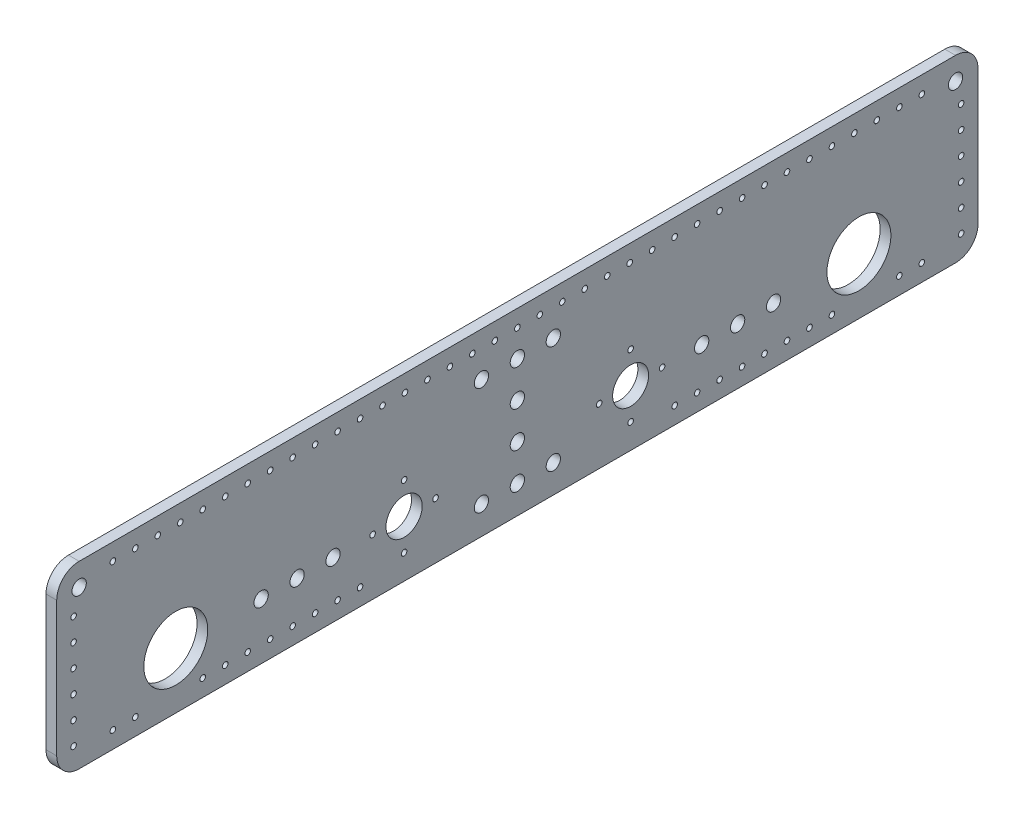
SolidWorks part; units mm, degrees
ref_plane "Front Plane" through (0, 0, 0) normal (0, 0, 1) x (1, 0, 0)
ref_plane "Top Plane" through (0, 0, 0) normal (0, 1, 0) x (1, 0, 0)
ref_plane "Right Plane" through (0, 0, 0) normal (1, 0, 0) x (0, 0, -1)
sketch "Sketch2" plane through (0, 0, 0) normal (1, 0, 0) x (0, 0, -1)
  line L0 (-23.4723, 28.6683) -> (-23.4723, -31.3317)
  line L1 (-13.4723, 38.6683) -> (376.5277, 38.6683)
  line L2 (-13.4723, -41.3317) -> (376.5277, -41.3317)
  line L3 (386.5277, 28.6683) -> (386.5277, -31.3317)
  circle A1 centre (29.5277, -16.3317) radius 14.225
  circle A2 centre (333.5277, -16.3317) radius 14.225
  arc A15 (-23.4723, 28.6683) -> (-13.4723, 38.6683) centre (-13.4723, 28.6683) cw
  arc A16 (-13.4723, -41.3317) -> (-23.4723, -31.3317) centre (-13.4723, -31.3317) cw
  arc A17 (386.5277, 28.6683) -> (376.5277, 38.6683) centre (376.5277, 28.6683) ccw
  arc A18 (376.5277, -41.3317) -> (386.5277, -31.3317) centre (376.5277, -31.3317) ccw
  circle A59 centre (181.5277, -28.7717) radius 3.18
  circle A60 centre (197.5277, -28.7717) radius 3.18
  circle A63 centre (197.5277, 19.2283) radius 3.18
  circle A64 centre (181.5277, -12.7717) radius 3.18
  circle A65 centre (181.5277, 3.2283) radius 3.18
  circle A66 centre (181.5277, 19.2283) radius 3.18
  circle A67 centre (165.5277, -28.7717) radius 3.18
  circle A68 centre (165.5277, 19.2283) radius 3.18
  circle A69 centre (197.5277, -12.7717) radius 3.18 [skipped]
  circle A70 centre (197.5277, 3.2283) radius 3.18 [skipped]
  circle A71 centre (-8.4723, 31.1683) radius 1.25 construction
  circle A150 centre (83.5027, -16.3317) radius 3.18
  circle A151 centre (279.5527, -16.3317) radius 3.18
  circle A152 centre (1.5277, 31.1683) radius 1.25
  circle A153 centre (11.5277, 31.1683) radius 1.25
  circle A154 centre (21.5277, 31.1683) radius 1.25
  circle A155 centre (31.5277, 31.1683) radius 1.25
  circle A156 centre (41.5277, 31.1683) radius 1.25
  circle A157 centre (51.5277, 31.1683) radius 1.25
  circle A158 centre (61.5277, 31.1683) radius 1.25
  circle A159 centre (71.5277, 31.1683) radius 1.25
  circle A160 centre (81.5277, 31.1683) radius 1.25
  circle A161 centre (91.5277, 31.1683) radius 1.25
  circle A162 centre (101.5277, 31.1683) radius 1.25
  circle A163 centre (111.5277, 31.1683) radius 1.25
  circle A164 centre (121.5277, 31.1683) radius 1.25
  circle A165 centre (131.5277, 31.1683) radius 1.25
  circle A166 centre (141.5277, 31.1683) radius 1.25
  circle A167 centre (151.5277, 31.1683) radius 1.25
  circle A168 centre (161.5277, 31.1683) radius 1.25
  circle A169 centre (171.5277, 31.1683) radius 1.25
  circle A170 centre (181.5277, 31.1683) radius 1.25
  circle A171 centre (191.5277, 31.1683) radius 1.25
  circle A172 centre (201.5277, 31.1683) radius 1.25
  circle A173 centre (211.5277, 31.1683) radius 1.25
  circle A174 centre (221.5277, 31.1683) radius 1.25
  circle A175 centre (231.5277, 31.1683) radius 1.25
  circle A176 centre (241.5277, 31.1683) radius 1.25
  circle A177 centre (251.5277, 31.1683) radius 1.25
  circle A178 centre (261.5277, 31.1683) radius 1.25
  circle A179 centre (271.5277, 31.1683) radius 1.25
  circle A180 centre (281.5277, 31.1683) radius 1.25
  circle A181 centre (291.5277, 31.1683) radius 1.25
  circle A182 centre (301.5277, 31.1683) radius 1.25
  circle A183 centre (311.5277, 31.1683) radius 1.25
  circle A184 centre (321.5277, 31.1683) radius 1.25
  circle A185 centre (331.5277, 31.1683) radius 1.25
  circle A186 centre (341.5277, 31.1683) radius 1.25
  circle A187 centre (351.5277, 31.1683) radius 1.25
  circle A188 centre (361.5277, 31.1683) radius 1.25
  circle A190 centre (1.5277, -33.8317) radius 1.25
  circle A191 centre (11.5277, -33.8317) radius 1.25
  circle A194 centre (41.5277, -33.8317) radius 1.25
  circle A195 centre (51.5277, -33.8317) radius 1.25
  circle A196 centre (61.5277, -33.8317) radius 1.25
  circle A197 centre (71.5277, -33.8317) radius 1.25
  circle A198 centre (81.5277, -33.8317) radius 1.25
  circle A199 centre (91.5277, -33.8317) radius 1.25
  circle A200 centre (101.5277, -33.8317) radius 1.25
  circle A201 centre (111.5277, -33.8317) radius 1.25
  circle A215 centre (251.5277, -33.8317) radius 1.25
  circle A216 centre (261.5277, -33.8317) radius 1.25
  circle A217 centre (271.5277, -33.8317) radius 1.25
  circle A218 centre (281.5277, -33.8317) radius 1.25
  circle A219 centre (291.5277, -33.8317) radius 1.25
  circle A220 centre (301.5277, -33.8317) radius 1.25
  circle A221 centre (311.5277, -33.8317) radius 1.25
  circle A222 centre (321.5277, -33.8317) radius 1.25
  circle A225 centre (351.5277, -33.8317) radius 1.25
  circle A226 centre (361.5277, -33.8317) radius 1.25
  circle A229 centre (181.5277, -33.8317) radius 1.25 [skipped]
  circle A230 centre (201.5277, -33.8317) radius 1.25 [skipped]
  circle A231 centre (161.5277, -33.8317) radius 1.25 [skipped]
  circle A232 centre (151.5277, -33.8317) radius 1.25 [skipped]
  circle A233 centre (141.5277, -33.8317) radius 1.25 [skipped]
  circle A234 centre (131.5277, -33.8317) radius 1.25 [skipped]
  circle A235 centre (171.5277, -33.8317) radius 1.25 [skipped]
  circle A236 centre (191.5277, -33.8317) radius 1.25 [skipped]
  circle A237 centre (211.5277, -33.8317) radius 1.25 [skipped]
  circle A238 centre (221.5277, -33.8317) radius 1.25 [skipped]
  circle A239 centre (231.5277, -33.8317) radius 1.25 [skipped]
  circle A240 centre (31.5277, -33.8317) radius 1.25 [skipped]
  circle A241 centre (21.5277, -33.8317) radius 1.25 [skipped]
  circle A242 centre (331.5277, -33.8317) radius 1.25 [skipped]
  circle A243 centre (341.5277, -33.8317) radius 1.25 [skipped]
  circle A245 centre (-13.4723, 28.6683) radius 3.18
  circle A247 centre (376.5277, 28.6683) radius 3.18
  circle A248 centre (371.5277, 31.1683) radius 1.25 [skipped]
  circle A249 centre (371.5277, -33.8317) radius 1.25 [skipped]
  circle A250 centre (-8.4723, -33.8317) radius 1.25 [skipped]
  circle A253 centre (99.5027, -16.3317) radius 3.18
  circle A254 centre (295.5527, -16.3317) radius 3.18
  circle A255 centre (67.5027, -16.3317) radius 3.18
  circle A256 centre (263.5527, -16.3317) radius 3.18
  circle A257 centre (121.5277, -33.8317) radius 1.25 [skipped]
  circle A260 centre (131.1277, -30.3317) radius 1.25
  circle A261 centre (145.1277, -16.3317) radius 1.25
  circle A262 centre (131.1277, -2.3317) radius 1.25
  circle A263 centre (117.1277, -16.3317) radius 1.25
  circle A264 centre (231.9277, -30.3317) radius 1.25
  circle A265 centre (217.9277, -16.3317) radius 1.25
  circle A266 centre (231.9277, -2.3317) radius 1.25
  circle A267 centre (245.9277, -16.3317) radius 1.25
  circle A268 centre (231.9277, -16.3317) radius 8
  circle A269 centre (131.1277, -16.3317) radius 8.0683
  circle A270 centre (241.5277, -33.8317) radius 1.25 [skipped]
  circle A271 centre (-15.9723, 18.6683) radius 1.25
  circle A272 centre (379.0277, 18.6683) radius 1.25
  circle A273 centre (379.0277, 8.6683) radius 1.25
  circle A274 centre (379.0277, -1.3317) radius 1.25
  circle A275 centre (379.0277, -11.3317) radius 1.25
  circle A276 centre (379.0277, -21.3317) radius 1.25
  circle A277 centre (379.0277, -31.3317) radius 1.25
  circle A278 centre (-15.9723, 8.6683) radius 1.25
  circle A279 centre (-15.9723, -1.3317) radius 1.25
  circle A280 centre (-15.9723, -11.3317) radius 1.25
  circle A281 centre (-15.9723, -21.3317) radius 1.25
  circle A282 centre (-15.9723, -31.3317) radius 1.25
  point P32 (-23.4723, 38.6683)
  point P35 (-23.4723, -41.3317)
  point P40 (386.5277, -41.3317)
  point P123 (181.5277, -41.3317)
  dimension "D3" = 25
  dimension "D7" = 10
  dimension "D8" = 10
  dimension "D9" = 10
  dimension "D10" = 10
  dimension "D11" = 7.5
  dimension "D13" = 12.56
  dimension "D20" = 7.5
  dimension "D1" = 80
  dimension "D2" = 410
  dimension "D4" = 53
  dimension "D5" = 25
  dimension "D6" = 53
  dimension "D12" = 15
  dimension "D14" = 205
  dimension "D21" = 20
  dimension "D15" = 2
  dimension "D16" = 4
  dimension "D17" = 2
  dimension "D18" = 39
  dimension "D19" = 2
  dimension "D22" = 2
  dimension "D23" = 2
  dimension "D24" = 2
  dimension "D25" = 6
extrude "Boss-Extrude1" add sketch "Sketch2" along normal blind 4.7625
